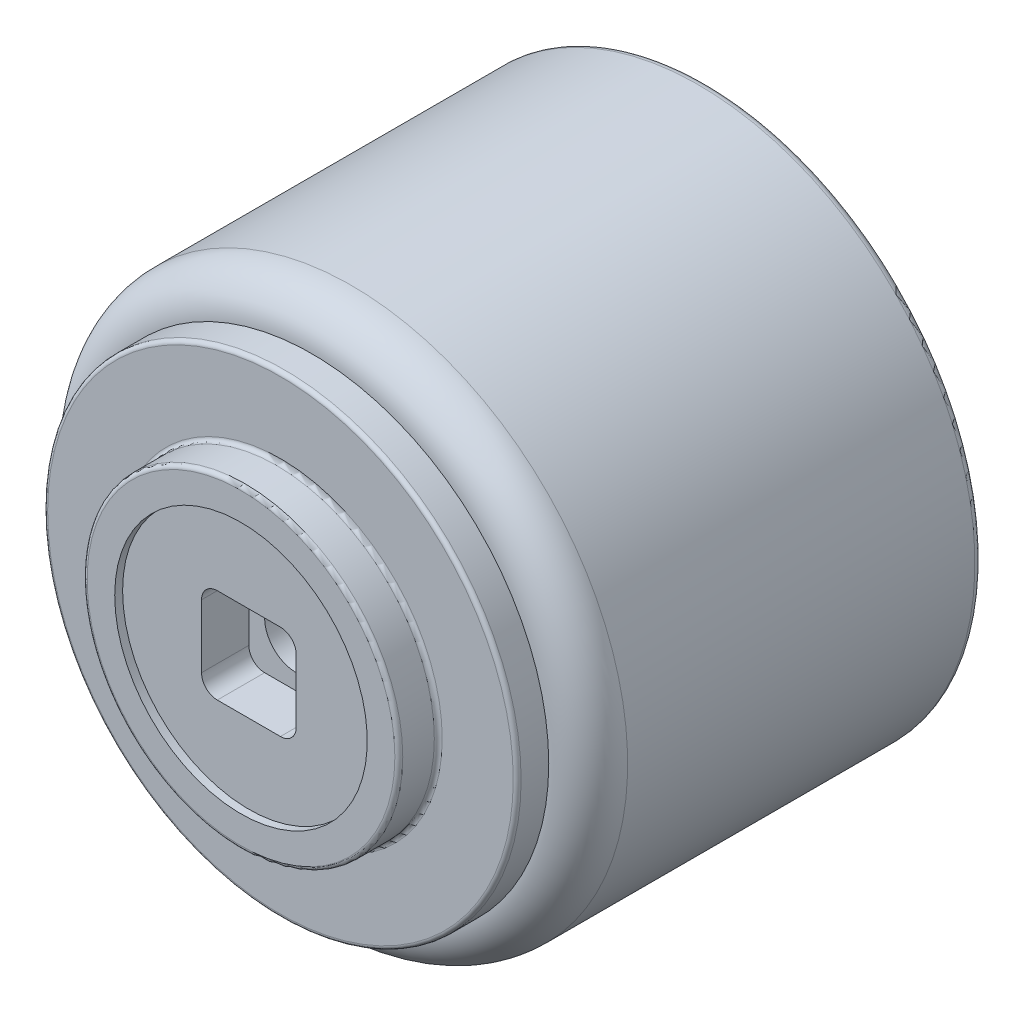
SolidWorks part; units mm, degrees
ref_plane "Front Plane" through (0, 0, 0) normal (0, 0, 1) x (1, 0, 0)
ref_plane "Top Plane" through (0, 0, 0) normal (0, 1, 0) x (1, 0, 0)
ref_plane "Right Plane" through (0, 0, 0) normal (1, 0, 0) x (0, 0, -1)
ref_plane "Plane1" through (0, 0, 0) normal (0, -1, 0) x (1, 0, 0)
sketch "Sketch1" plane through (0, 0, 0) normal (0, -1, 0) x (1, 0, 0)
  line L0 (30, 54) -> (0, 54)
  line L1 (0, 54) -> (0, 0)
  line L2 (0, 0) -> (35, 0)
  line L3 (35, 0) -> (35, 45)
  line L4 (30, 50) -> (30, 54)
  line L5 (0, 54) -> (0, 0) construction
  arc A0 (35, 45) -> (30, 50) centre (30, 45) ccw
revolve "Revolve1" add sketch "Sketch1" angle 360 about L5 reverse direction yes
sketch "Sketch2" plane through (0, 0, 54) normal (0, 0, 1) x (1, 0, 0)
  circle A0 centre (0, 0) radius 20
extrude "Boss-Extrude1" add sketch "Sketch2" along normal blind 5
sketch "Sketch3" plane through (0, 0, 59) normal (0, 0, 1) x (1, 0, 0)
  line L0 (-6, 6) -> (-6, -6)
  line L1 (-6, -6) -> (6, -6)
  line L2 (6, -6) -> (6, 6)
  line L3 (6, 6) -> (-6, 6)
extrude "Cut-Extrude1" cut sketch "Sketch3" against normal blind 7
hole_wizard "M45 Clearance Hole1" positions "Sketch5" profile "Sketch4" hole size "M45" standard "ANSI Metric"
sketch "Sketch5" plane through (0, 0, 0) normal (0, 0, -1) x (-1, 0, 0)
  point P0 (0, 0)
sketch "Sketch4" plane through (0, 0, 0) normal (1, 0, 0) x (0, 1, 0)
  line L0 (0, 0) -> (0, 3)
  line L1 (0, 3) -> (25, 3)
  line L2 (25, 3) -> (25, 0)
  line L5 (25, 0) -> (0, 0)
  line L10 (0, 3) -> (-25, 3) construction
  line L11 (0, -6.35) -> (0, 107.95) construction
  dimension "Hole Dia." = 50
  dimension "Hole Depth" = 3
  dimension "Drill Angle" = 180
sketch "Sketch6" plane through (0, 0, 0) normal (0, 1, 0) x (1, 0, 0)
  line L0 (12.5, -1) -> (0, -1)
  line L1 (0, -1) -> (0, -3)
  line L2 (0, -3) -> (12.5, -3)
  line L3 (12.5, -3) -> (12.5, -1)
  line L4 (0, -1) -> (0, -3) construction
revolve "Revolve2" add sketch "Sketch6" angle 360 about L4 reverse direction yes
sketch "Sketch7" plane through (0, 0, 0) normal (0, 1, 0) x (1, 0, 0)
  line L0 (-16, -59) -> (0, -59)
  line L1 (0, -59) -> (0, -58)
  line L2 (0, -58) -> (-16, -58)
  line L3 (-16, -58) -> (-16, -59)
  line L4 (0, -59) -> (0, -58) construction
revolve "Cut-Revolve1" cut sketch "Sketch7" angle 360 about L4 reverse direction yes
hole_wizard "Ø8.0 (8) Diameter Hole1" positions "Sketch9" profile "Sketch8" hole size "Ø8.0" standard "ANSI Metric"
sketch "Sketch9" plane through (0, 0, 52) normal (0, 0, 1) x (1, 0, 0)
  point P0 (0, 0)
sketch "Sketch8" plane through (0, 0, 52) normal (1, 0, 0) x (0, -1, 0)
  line L0 (0, 0) -> (0, 52)
  line L1 (0, 52) -> (4, 52)
  line L2 (4, 52) -> (4, 0)
  line L5 (4, 0) -> (0, 0)
  line L11 (0, -6.35) -> (0, 107.95) construction
  dimension "Thru Hole Dia." = 8
  dimension "Thru Hole Depth" = 52
fillet "Fillet1" radius 0.5 7 edges at (-30, 0, 54) (12.5, 0, 1) (-25, 0, 0) (20, 0, 54) (-25, 0, 3) (20, 0, 59) (12.5, 0, 3) tangent propagation no
fillet "Fillet2" radius 1 1 edges at (-35, 0, 0) tangent propagation no
fillet "Fillet3" radius 2 4 edges at (-6, -6, 55) (6, -6, 55) (-6, 6, 55) (6, 6, 55) tangent propagation no
